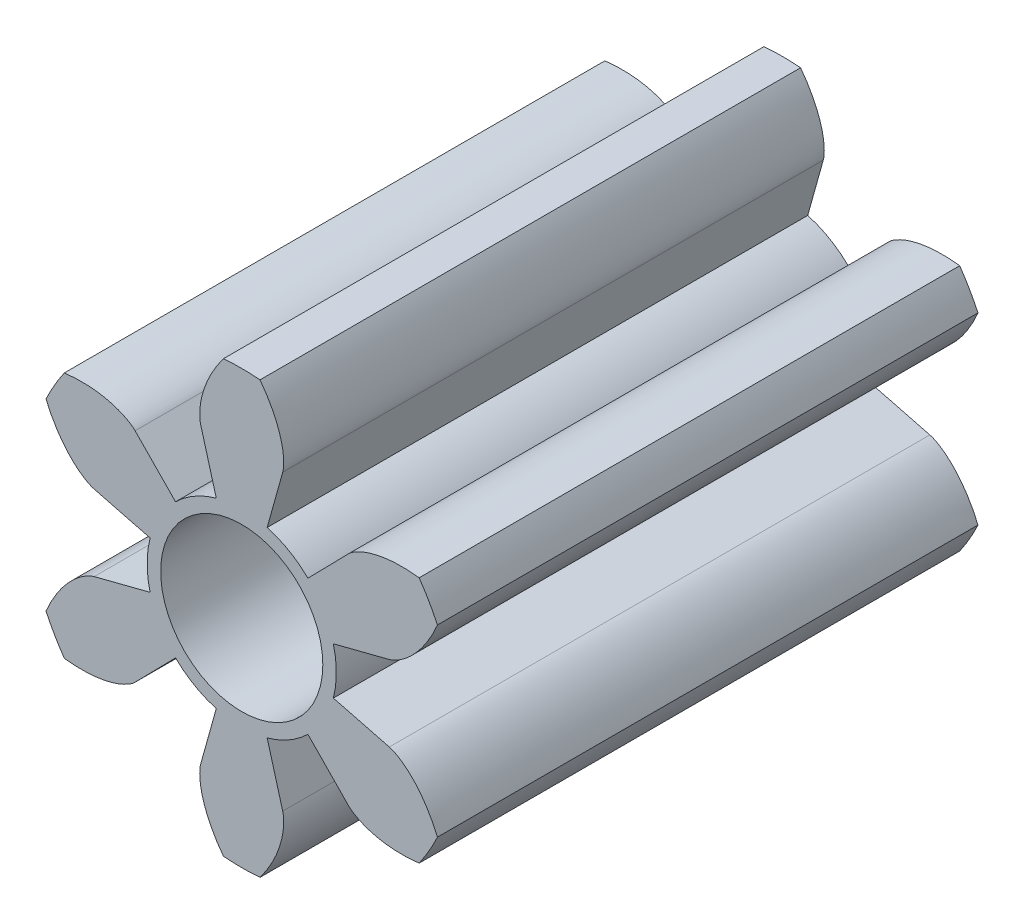
SolidWorks part; units mm, degrees
ref_plane "前视基准面" through (0, 0, 0) normal (0, 0, 1) x (1, 0, 0)
ref_plane "上视基准面" through (0, 0, 0) normal (0, 1, 0) x (1, 0, 0)
ref_plane "右视基准面" through (0, 0, 0) normal (1, 0, 0) x (0, 0, -1)
other "Configuration Table"
sketch "草图1" plane through (0, 0, 0) normal (0, 0, 1) x (1, 0, 0)
  line L0 (0, 0) -> (3, 0) construction
  line L1 (0, 0) -> (2.8978, 0.7765) construction
  line L2 (0, 0) -> (2.7305, 0.701)
  line L3 (2.8978, 0.7765) -> (2.8978, -0.7765) construction
  line L4 (0, 0) -> (2.7305, -0.701)
  circle A0 centre (0, 0) radius 4
  circle A1 centre (0, 0) radius 3 construction
  circle A2 centre (0, 0) radius 1.75
  circle A3 centre (0, 0) radius 2.8191 construction
  circle A4 centre (0, 0) radius 1.5
  spline S0 degree 4 poles (2.7305, 0.701) (2.7514, 0.7063) (2.8083, 0.7255) (2.9105, 0.779) (3.0627, 0.8875) (3.236, 1.0573) (3.4253, 1.3046) (3.6012, 1.6247) (3.742, 2.0003) (3.8364, 2.4221) (3.8779, 2.852) (3.8707, 3.2837) (3.8157, 3.7334) (3.69, 4.2802) (3.4574, 4.9086) (3.0836, 5.5918) (2.5556, 6.2772) (1.9356, 6.8796) (1.2391, 7.3923) (0.4849, 7.8122) (-0.3175, 8.1368) (-1.1468, 8.3674) (-2.0054, 8.5023) (-2.7502, 8.5427) (-3.4127, 8.5171) (-3.8849, 8.4708) (-4.3024, 8.4076) (-4.5772, 8.3558) (-4.9624, 8.2714) (-5.2496, 8.1908) (-5.5362, 8.1071) (-5.6783, 8.056) (-5.7704, 8.0254) knots 0 0 0 0 0 0.005604 0.015718 0.02996 0.048734 0.068727 0.096889 0.125051 0.153212 0.181374 0.209535 0.237696 0.271429 0.327752 0.384075 0.440398 0.496721 0.553044 0.609367 0.66569 0.722013 0.778336 0.834659 0.86282 0.890982 0.909091 0.931818 0.954545 0.977273 1 1 1 1 1 construction
  spline S1 degree 4 poles (2.7305, 0.701) (2.7514, 0.7063) (2.8083, 0.7255) (2.9105, 0.779) (3.0627, 0.8875) (3.236, 1.0573) (3.4253, 1.3046) (3.6012, 1.6247) (3.742, 2.0003) (3.8364, 2.4221) (3.8779, 2.852) (3.8707, 3.2837) (3.8157, 3.7334) (3.69, 4.2802) (3.4574, 4.9086) (3.0836, 5.5918) (2.5556, 6.2772) (1.9356, 6.8796) (1.2391, 7.3923) (0.4849, 7.8122) (-0.3175, 8.1368) (-1.1468, 8.3674) (-2.0054, 8.5023) (-2.7502, 8.5427) (-3.4127, 8.5171) (-3.8849, 8.4708) (-4.2047, 8.4224) (-4.3632, 8.395) (-4.4251, 8.3835) knots 0 0 0 0 0 0.005604 0.015718 0.02996 0.048734 0.068727 0.096889 0.125051 0.153212 0.181374 0.209535 0.237696 0.271429 0.327752 0.384075 0.440398 0.496721 0.553044 0.609367 0.66569 0.722013 0.778336 0.834659 0.86282 0.890982 0.909091 0.909091 0.909091 0.909091 0.909091
  spline S2 degree 4 poles (2.7305, -0.701) (2.7514, -0.7063) (2.8083, -0.7255) (2.9105, -0.779) (3.0627, -0.8875) (3.236, -1.0573) (3.4253, -1.3046) (3.6012, -1.6247) (3.742, -2.0003) (3.8364, -2.4221) (3.8779, -2.852) (3.8707, -3.2837) (3.8157, -3.7334) (3.69, -4.2802) (3.4574, -4.9086) (3.0836, -5.5918) (2.5556, -6.2772) (1.9356, -6.8796) (1.2391, -7.3923) (0.4849, -7.8122) (-0.3175, -8.1368) (-1.1468, -8.3674) (-2.0054, -8.5023) (-2.7502, -8.5427) (-3.4127, -8.5171) (-3.8849, -8.4708) (-4.3024, -8.4076) (-4.5772, -8.3558) (-4.9624, -8.2714) (-5.2496, -8.1908) (-5.5362, -8.1071) (-5.6783, -8.056) (-5.7704, -8.0254) knots 0 0 0 0 0 0.005604 0.015718 0.02996 0.048734 0.068727 0.096889 0.125051 0.153212 0.181374 0.209535 0.237696 0.271429 0.327752 0.384075 0.440398 0.496721 0.553044 0.609367 0.66569 0.722013 0.778336 0.834659 0.86282 0.890982 0.909091 0.931818 0.954545 0.977273 1 1 1 1 1 construction
  spline S3 degree 4 poles (2.7305, -0.701) (2.7514, -0.7063) (2.8083, -0.7255) (2.9105, -0.779) (3.0627, -0.8875) (3.236, -1.0573) (3.4253, -1.3046) (3.6012, -1.6247) (3.742, -2.0003) (3.8364, -2.4221) (3.8779, -2.852) (3.8707, -3.2837) (3.8157, -3.7334) (3.69, -4.2802) (3.4574, -4.9086) (3.0836, -5.5918) (2.5556, -6.2772) (1.9356, -6.8796) (1.2391, -7.3923) (0.4849, -7.8122) (-0.3175, -8.1368) (-1.1468, -8.3674) (-2.0054, -8.5023) (-2.7502, -8.5427) (-3.4127, -8.5171) (-3.8849, -8.4708) (-4.2047, -8.4224) (-4.3632, -8.395) (-4.4251, -8.3835) knots 0 0 0 0 0 0.005604 0.015718 0.02996 0.048734 0.068727 0.096889 0.125051 0.153212 0.181374 0.209535 0.237696 0.271429 0.327752 0.384075 0.440398 0.496721 0.553044 0.609367 0.66569 0.722013 0.778336 0.834659 0.86282 0.890982 0.909091 0.909091 0.909091 0.909091 0.909091
  point P15 (2.8978, 0)
  dimension "齿顶圆直径" = 8
  dimension "分度圆直径" = 6
  dimension "齿根圆直径" = 3.5
  dimension "基圆直径" = 5.6382
  dimension "内孔直径" = 3
  dimension "渐近线镜像线夹角" = 15
extrude "凸台-拉伸1" add sketch "草图1" along normal blind 10 contours A0 | A4
extrude "切除-拉伸1" cut sketch "草图1<3>" along normal through all contours A2 S3 A0 S1 region at (3.0753, 0, 0)
sketch "草图1<3>" plane through (0, 0, 0) normal (0, 0, 1) x (1, 0, 0) same geometry as "草图1"
pattern_circular "阵列(圆周)1" count 6 every 60 about axis through (0, 0, 10) along (0, 0, 1) of "切除-拉伸1"
equation "\"m\"= 1'模数"
equation "\"z\"= 6'齿数"
equation "\"a\"= 20度'压力角"
equation "\"d\"= \"m\" * \"z\"'分度圆直径"
equation "\"da\"= ( \"z\" + 2 ) * \"m\"'齿顶圆直径"
equation "\"df\"= ( \"z\" - 2.5 ) * \"m\"'齿根圆直径"
equation "\"s\"= 0.5 * PI * \"m\"'分度圆齿厚"
equation "\"r\"= 0.38 * \"m\"'齿根圆角"
equation "\"B\"= 0.3 * \"d\"'齿厚"
equation "\"db\"= \"m\" * \"z\" * cos ( \"a\" )'基圆直径"
equation "\"rb\"= \"db\" / 2'基圆半径"
equation "\"齿顶圆直径@草图1\"= \"da\""
equation "\"分度圆直径@草图1\"= \"d\""
equation "\"齿根圆直径@草图1\"= \"df\""
equation "\"基圆直径@草图1\"= \"db\""
equation "\"渐近线镜像线夹角@草图1\"= 360 / 4 / \"z\""
equation "\"h\"= 10'齿轮厚度"
equation "\"ir\"= 3'内孔直径"
equation "\"内孔直径@草图1\"= \"ir\""
equation "\"齿轮厚@凸台-拉伸1\"= \"h\""
equation "\"齿轮夹角@阵列(圆周)1\"= 360 / \"z\""
equation "\"齿数@阵列(圆周)1\"= \"z\""
